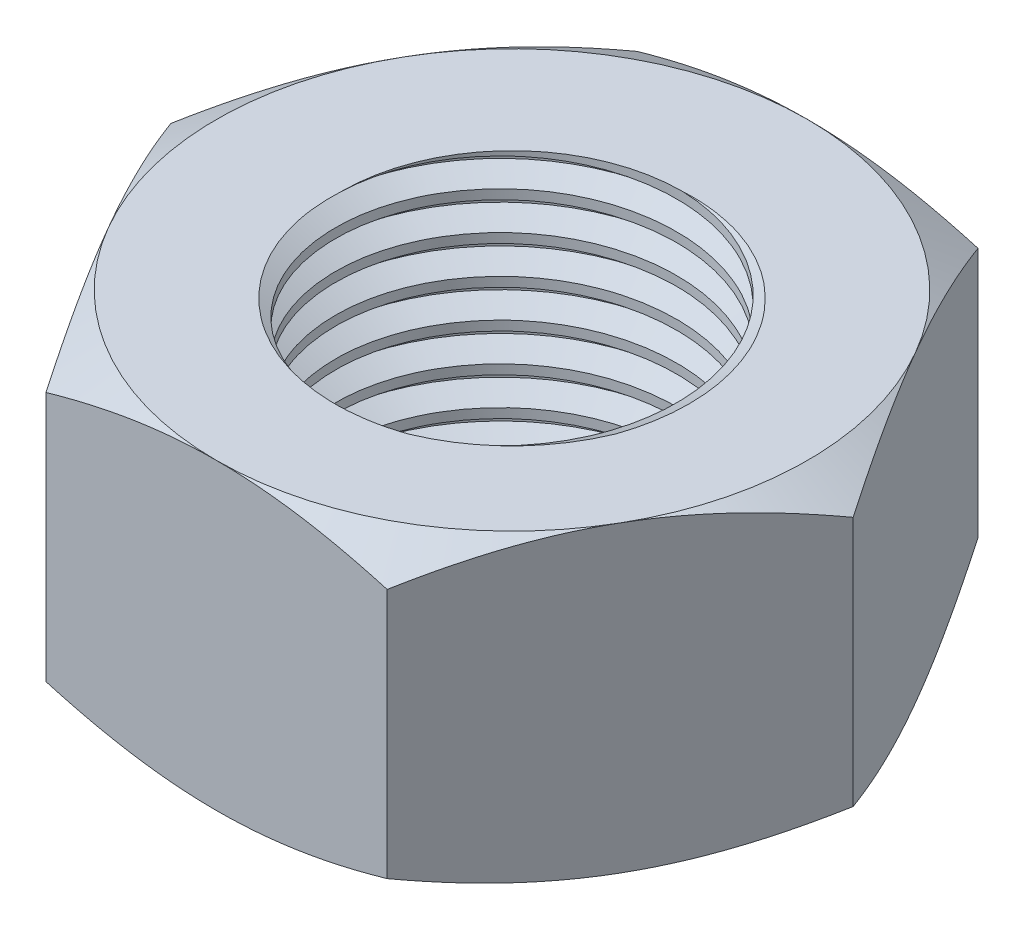
SolidWorks part; units mm, degrees
ref_plane "Front Plane" through (0, 0, 0) normal (0, 0, 1) x (1, 0, 0)
ref_plane "Top Plane" through (0, 0, 0) normal (0, 1, 0) x (1, 0, 0)
ref_plane "Right Plane" through (0, 0, 0) normal (1, 0, 0) x (0, 0, -1)
sketch "Sketch1" plane through (0, 0, 0) normal (0, 1, 0) x (1, 0, 0)
  line L1 (4.5, -7.7942) -> (9, 0)
  line L2 (9, 0) -> (4.5, 7.7942)
  line L3 (4.5, 7.7942) -> (-4.5, 7.7942)
  line L4 (-4.5, 7.7942) -> (-9, 0)
  line L5 (-9, 0) -> (-4.5, -7.7942)
  line L6 (-4.5, -7.7942) -> (4.5, -7.7942)
  circle A0 centre (0, 0) radius 7.7942 construction
  dimension "D1" = 18
extrude "Boss-Extrude1" add sketch "Sketch1" along normal blind 8
sketch "Sketch2" plane through (0, 0, 0) normal (1, 0, 0) x (0, 0, -1)
  line L0 (0, 0) -> (0, -50000) construction
  line L1 (7.7942, 0) -> (10.1517, 1.3611)
  line L2 (10.1517, 1.3611) -> (10.1517, 0)
  line L3 (10.1517, 0) -> (7.7942, 0)
  line L4 (-7.7942, 4) -> (7.7942, 4) construction
  line L5 (-7.7942, 8) -> (-7.7942, 0) construction
  line L6 (7.7942, 8) -> (7.7942, 0) construction
  line L7 (10.1517, 6.6389) -> (10.1517, 8)
  line L8 (10.1517, 8) -> (7.7942, 8)
  line L9 (7.7942, 8) -> (10.1517, 6.6389)
  dimension "D1" = 30
revolve "Cut-Revolve1" cut sketch "Sketch2" angle 360 about L0
hole_wizard "M10x1.0 Tapped Hole1" positions "Sketch3" profile "Sketch4" tap size "M10x1.0" standard "ANSI Metric" end condition up to next
sketch "Sketch3" plane through (0, 8, 0) normal (0, 1, 0) x (1, 0, 0)
  point P0 (0, 0)
sketch "Sketch4" plane through (0, 8, 0) normal (1, 0, 0) x (0, 0, 1)
  line L0 (0, 0) -> (0, 8)
  line L1 (0, 8) -> (4.5, 8)
  line L2 (4.5, 8) -> (4.5, 0)
  line L5 (4.5, 0) -> (0, 0)
  line L11 (0, -6.35) -> (0, 107.95) construction
  dimension "Thru Tap Drill Dia." = 9
  dimension "Thru Tap Drill Depth" = 8
cosmetic thread "Hole Thread1" parameters "D2"=10
thread "Thread1" pitch 1 method cut profile "Thread Profile1" start angle 0, offset 1, length 0, pitch 1, diameter 9
ref_plane "Plane1" through (-4.5, 9, 0) normal (0, 0, 1) x (-1, 0, 0)
sketch "Thread Profile1" plane through (-4.5, 9, 0) normal (0, 0, 1) x (-1, 0, 0)
  line L0 (0, 0) -> (0, 1) construction
  line L1 (0, 0) -> (0.5413, 0.3125)
  line L2 (0.5413, 0.3125) -> (0.5413, 0.4375)
  line L3 (0.5413, 0.4375) -> (0, 0.75)
  line L4 (0.5413, 0.375) -> (0, 0.375) construction
  line L11 (0, 0) -> (0, 0.75)
  point P2 (0, 0)
  dimension "Pitch" = 1
  dimension "Profile_Angle" = 60
  dimension "Profile_Land" = 0.125
  dimension "Profile_Height" = 0.5413
